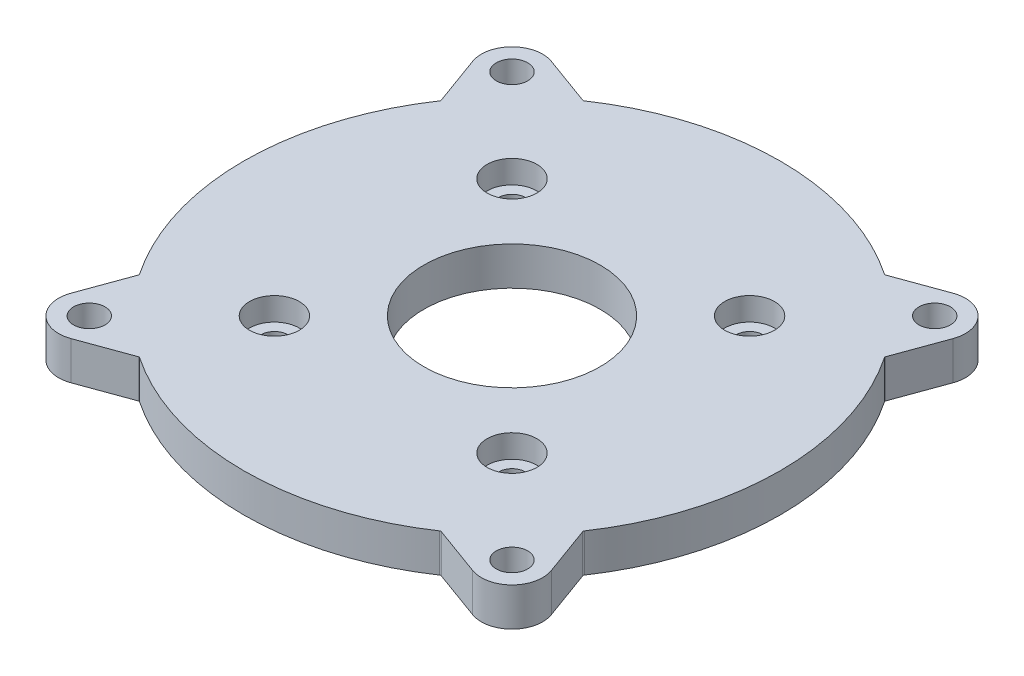
SolidWorks part; units mm, degrees
note: The reader was unsure of these and kept them because the rebuilt part matched: shared geometry of "Sketch2<4>", "Sketch2<5>".
ref_plane "Front Plane" through (0, 0, 0) normal (0, 0, 1) x (1, 0, 0)
ref_plane "Top Plane" through (0, 0, 0) normal (0, 1, 0) x (1, 0, 0)
ref_plane "Right Plane" through (0, 0, 0) normal (1, 0, 0) x (0, 0, -1)
sketch "Sketch1" plane through (0, 0, 0) normal (0, 1, 0) x (1, 0, 0)
  circle A3 centre (0, 0) radius 35
  dimension "D5" = 70
extrude "Boss-Extrude1" add sketch "Sketch1" along normal blind 5 contours A3
sketch "Sketch2" plane through (0, 5, 0) normal (0, 1, 0) x (1, 0, 0)
  line L0 (0, 0) -> (15.4998, 15.4998)
  circle A0 centre (0, 0) radius 21.92
  circle A1 centre (15.4998, 15.4998) radius 3.25
  circle A2 centre (15.4998, 15.4998) radius 1.75
  circle A3 centre (0, 0) radius 11.5
  dimension "D1" = 43.84
  dimension "D2" = 6.5
  dimension "D4" = 3.5
  dimension "D5" = 23
  dimension "D3" = 45
extrude "Cut-Extrude1" cut sketch "Sketch2" against normal through all contours A3
extrude "Cut-Extrude2" cut sketch "Sketch2<4>" against normal blind 3 contours A2 A0 A1 | A2 L0 A1 A0 | A2 A0 A1 L0
sketch "Sketch2<4>" plane through (0, 5, 0) normal (0, 1, 0) x (1, 0, 0) same geometry as "Sketch2"
extrude "Cut-Extrude3" cut sketch "Sketch2<5>" against normal through all contours A2
sketch "Sketch2<5>" plane through (0, 5, 0) normal (0, 1, 0) x (1, 0, 0) same geometry as "Sketch2"
pattern_circular "CirPattern3" count 4 over 360 about axis through (0, 0, 0) along (0, 1, 0) of "Cut-Extrude2", "Cut-Extrude3"
sketch "Sketch3" plane through (0, 5, 0) normal (0, 1, 0) x (1, 0, 0)
  line L0 (0, 0) -> (27.5772, 27.5772) construction
  line L1 (26.2091, 31.3359) -> (19.6642, 28.9538)
  line L2 (31.3359, 26.2091) -> (28.9538, 19.6642)
  circle A0 centre (27.5772, 27.5772) radius 4
  circle A1 centre (0, 0) radius 35
  circle A2 centre (0, 0) radius 35
  circle A3 centre (27.5772, 27.5772) radius 2.05
  dimension "D2" = 8
  dimension "D3" = 4.1
  dimension "D4" = 45
  dimension "D5" = 25
  dimension "D1" = 0
extrude "Boss-Extrude2" add sketch "Sketch3" against normal up to surface (5 mm away)
fillet "Fillet1" radius 0.2 2 edges at (19.6642, 2.5, -28.9538) (28.9538, 2.5, -19.6642)
pattern_circular "CirPattern4" count 4 over 360 about axis through (0, 0, 0) along (0, 1, 0) of "Boss-Extrude2", "Fillet1"
